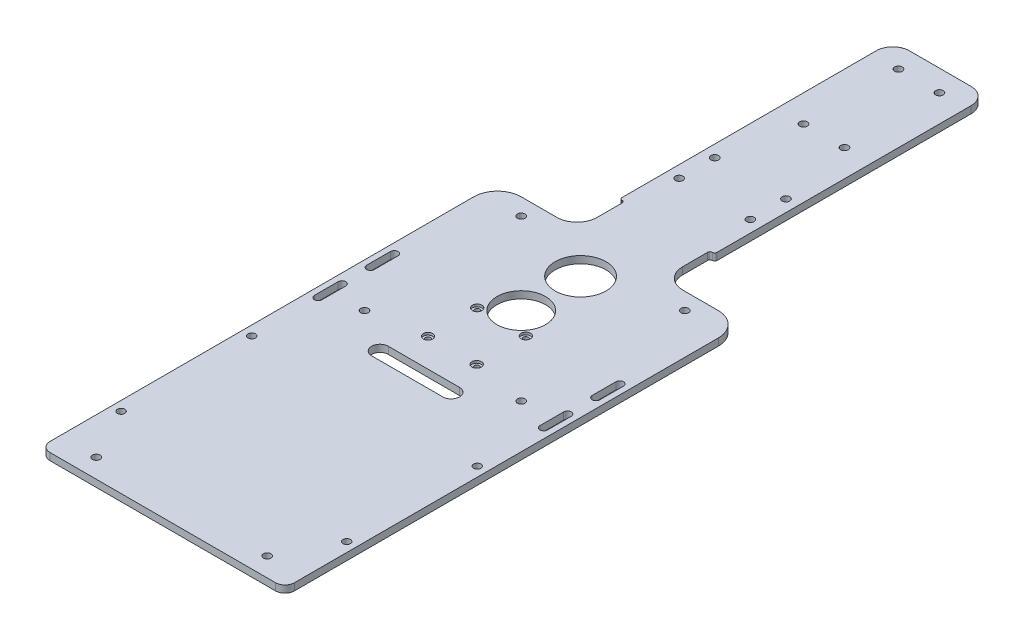
SolidWorks part; units mm, degrees
material "Hexcel AS4C (3000 丝)"
ref_plane "前视基准面" through (0, 0, 0) normal (0, 0, 1) x (1, 0, 0)
ref_plane "上视基准面" through (0, 0, 0) normal (0, 1, 0) x (1, 0, 0)
ref_plane "右视基准面" through (0, 0, 0) normal (1, 0, 0) x (0, 0, -1)
sketch "草图1" plane through (0, 0, 0) normal (0, 1, 0) x (1, 0, 0)
  line L1 (-100, 100) -> (100, 100)
  line L2 (-100, 100) -> (-100, -100)
  line L3 (-100, -100) -> (100, -100)
  line L4 (100, 100) -> (100, -100)
  line L5 (-100, 100) -> (100, -100) construction
  line L6 (-100, -100) -> (100, 100) construction
  point P0 (0, 0)
  dimension "D1" = 200
  dimension "D2" = 200
extrude "凸台-拉伸1" add sketch "草图1" along normal blind 3
sketch "草图2" plane through (0, 3, 0) normal (0, 1, 0) x (1, 0, 0)
  line L0 (0, 0) -> (0, 91) construction
  line L1 (-100, -100) -> (100, -100) construction
  line L2 (100, 100) -> (-100, 100) construction
  line L3 (-100, 0) -> (100, 0) construction
  line L5 (-100, 100) -> (-100, -100) construction
  line L6 (100, -100) -> (100, 100) construction
  line L7 (-29.5, 0) -> (29.5, 0) construction
  line L8 (-10, 100) -> (10, 100) construction
  line L9 (-10, 100) -> (-10, -100) construction
  line L10 (10, 100) -> (10, -100) construction
  line L11 (0, 0) -> (0, -29) construction
  line L13 (0, -29) -> (0, -32) construction
  circle A0 centre (-29.5, 0) radius 22.5 construction
  circle A1 centre (29.5, 0) radius 22.5 construction
  circle A2 centre (0, -29) radius 10.05 construction
  circle A3 centre (29.5, 0) radius 9.5 construction
  circle A4 centre (29.5, 0) radius 8 construction
  circle A5 centre (-29.5, 0) radius 8 construction
  circle A6 centre (-29.5, 0) radius 9.5 construction
  circle A7 centre (29.5, 9.5) radius 1.5
  circle A8 centre (21.5, 0) radius 1.5
  circle A9 centre (29.5, -9.5) radius 1.5
  circle A10 centre (37.5, 0) radius 1.5
  circle A11 centre (-29.5, -9.5) radius 1.5
  circle A12 centre (-37.5, 0) radius 1.5
  circle A13 centre (-21.5, 0) radius 1.5
  circle A14 centre (-29.5, 9.5) radius 1.5
  point P16 (0, 0)
  dimension "D1" = 45
  dimension "D3" = 20.1
  dimension "D4" = 19
  dimension "D5" = 16
  dimension "D6" = 3
  dimension "D7" = 3
  dimension "D2" = 20
  dimension "D9" = 3
  dimension "D10" = 29
extrude "切除-拉伸2" cut sketch "草图2" against normal blind 10
sketch "草图4" plane through (0, 3, 0) normal (0, 1, 0) x (1, 0, 0)
  line L0 (0, 0) -> (0, 91) construction
  line L1 (100, 100) -> (-100, 100) construction
  line L2 (-10, 100) -> (10, 100)
  line L3 (-10, 100) -> (-10, -100) construction
  line L4 (-100, -100) -> (100, -100) construction
  line L5 (10, 100) -> (10, -100) construction
  line L6 (21.5, 0) -> (37.5, 0)
  line L7 (-29.5, 0) -> (0, 0) construction
  line L8 (0, -29) -> (0, 0) construction
  circle A0 centre (0, -29) radius 10.7
  circle A1 centre (29.5, 0) radius 8 construction
  circle A2 centre (29.5, 0) radius 9.5 construction
  circle A3 centre (29.5, 0) radius 22.5 construction
  circle A4 centre (-29.5, 0) radius 9.5 construction
  circle A5 centre (-29.5, 0) radius 8 construction
  circle A6 centre (-29.5, 0) radius 22.5 construction
  dimension "D1" = 21.4
  dimension "D2" = 19
  dimension "D3" = 16
  dimension "D4" = 45
sketch "草图5" plane through (0, 3, 0) normal (0, 1, 0) x (1, 0, 0)
  line L0 (-44.5, -100) -> (-100, -100)
  line L2 (44.5, 0) -> (44.5, -100)
  line L4 (-20, 47.5) -> (-20, 24.995)
  line L6 (-44.5, 0) -> (-44.5, -100)
  line L7 (-100, -100) -> (100, -100) construction
  line L8 (20, 47.5) -> (20, 24.995)
  line L9 (-100, -100) -> (-100, 100)
  line L10 (0, 0) -> (0, 91) construction
  line L11 (0, 47.5) -> (-20, 47.5)
  line L12 (44.5, -100) -> (-44.5, -100)
  line L13 (0, 47.5) -> (20, 47.5)
  line L14 (-100, 100) -> (100, 100)
  line L15 (100, 100) -> (100, -100)
  line L16 (100, -100) -> (44.5, -100)
  arc A0 (29.8, 14.997) -> (44.5, 0) centre (29.5, 0) cw
  arc A1 (20, 24.995) -> (29.8, 14.997) centre (30, 24.995) ccw
  arc A2 (-29.8, 14.997) -> (-44.5, 0) centre (-29.5, 0) ccw
  arc A3 (-20, 24.995) -> (-29.8, 14.997) centre (-30, 24.995) cw
  line M11 (100, -100) -> (100, 100)
  line M12 (100, 100) -> (-100, 100)
  line M13 (-100, 100) -> (-100, -100)
  line M14 (-100, -100) -> (100, -100)
  dimension "D1" = 10
  dimension "D2" = 15
extrude "切除-拉伸3" cut sketch "草图5" against normal blind 10 contours A3 L4 L11 L13 L8 A1 A0 L2 L6 A2 M14 M11 M12 M13 region at (-72.25, 3, 97.1716)
sketch "草图6" plane through (0, 0, 0) normal (0, -1, 0) x (1, 0, 0)
  line L0 (20, -47.5) -> (-20, -47.5) construction
  line L7 (-20, -47.5) -> (-20, -24.995) construction
  circle A1 centre (-15, -42.5) radius 1.6
  circle A2 centre (-15, -27.5) radius 1.6
  circle A3 centre (15, -27.5) radius 1.6
  circle A4 centre (15, -42.5) radius 1.6
  dimension "D1" = 3.2
  dimension "D5" = 3.2
  dimension "D6" = 3.2
  dimension "D7" = 3.2
  dimension "D2" = 5
  dimension "D3" = 5
  dimension "D4" = 30
extrude "φ3.1通孔1" cut sketch "草图6" against normal blind 10
sketch "草图9" plane through (0, 3, 0) normal (0, 1, 0) x (1, 0, 0)
  line L0 (-20, 47.5) -> (-20, 26.3383)
  line L4 (-20, 47.5) -> (20, 47.5)
  line L5 (20, 47.5) -> (20, 26.3383)
  line L8 (12.2609, 20.995) -> (-12.2609, 20.995)
  arc A0 (-18.8003, 24.5054) -> (-13.4605, 21.3948) centre (-29.5, 0) cw
  arc A1 (18.8003, 24.5054) -> (13.4605, 21.3948) centre (29.5, 0) ccw
  arc A2 (18.8003, 24.5054) -> (20, 26.3383) centre (18, 26.3383) ccw
  arc A3 (13.4605, 21.3948) -> (12.2609, 20.995) centre (12.2609, 22.995) cw
  arc A4 (-12.2609, 20.995) -> (-13.4605, 21.3948) centre (-12.2609, 22.995) cw
  arc A5 (-18.8003, 24.5054) -> (-20, 26.3383) centre (-18, 26.3383) cw
  point P20 (-20, 24.995)
  dimension "D1" = 2
sketch "草图11" plane through (0, 3, 0) normal (0, 1, 0) x (1, 0, 0)
  line L0 (44.5, -17.5) -> (44.5, -100)
  line L1 (20, 47.5) -> (20, 7.5)
  line L2 (-44.5, 0) -> (-44.5, -100) construction
  line L3 (-44.5, -17.5) -> (-44.5, -100)
  line L4 (0, 47.5) -> (0, -100) construction
  line L5 (20, 47.5) -> (-20, 47.5) construction
  line L6 (-44.5, -100) -> (44.5, -100) construction
  line L7 (18, -4) -> (18, 6.5)
  line L8 (20, 7.5) -> (19, 7.5)
  line L9 (-39.5, -12.5) -> (-44.5, -12.5)
  line L10 (26.5, -12.5) -> (39.5, -12.5)
  line L11 (20, 47.5) -> (101.1331, 47.5)
  line L12 (101.1331, 47.5) -> (101.1331, -100)
  line L13 (101.1331, -100) -> (44.5, -100)
  line L14 (-20, 47.5) -> (-20, 7.5)
  line L15 (-20, 7.5) -> (-19, 7.5)
  line L16 (-18, -4) -> (-18, 6.5)
  line L17 (-26.5, -12.5) -> (-39.5, -12.5)
  line L18 (-44.5, -12.5) -> (-44.5, -17.5)
  line L19 (-101.1331, -100) -> (-44.5, -100)
  line L20 (-101.1331, 47.5) -> (-101.1331, -100)
  line L21 (-20, 47.5) -> (-101.1331, 47.5)
  line L22 (39.5, -12.5) -> (44.5, -12.5)
  line L23 (44.5, 0) -> (44.5, -100) construction
  line L24 (44.5, -12.5) -> (44.5, -17.5)
  arc A0 (26.5, -12.5) -> (18, -4) centre (26.5, -4) cw
  circle A2 centre (29.5, -9.5) radius 1.5
  circle A4 centre (21.5, 0) radius 1.5
  arc A5 (18, 6.5) -> (19, 7.5) centre (19, 6.5) cw
  arc A6 (-18, 6.5) -> (-19, 7.5) centre (-19, 6.5) ccw
  arc A7 (-26.5, -12.5) -> (-18, -4) centre (-26.5, -4) ccw
  point P21 (-44.5, -12.5)
  dimension "D1" = 8.5
  dimension "D2" = 1
extrude "切除-拉伸6" cut sketch "草图11" against normal up to next
extrude "φ21.4落弹孔" cut sketch "草图4" against normal up to next contours A0 region at (0, 3, 29)
fillet "圆角1" radius 1 2 edges at (-20, 1.5, -7.5) (20, 1.5, -7.5)
sketch "草图12" plane through (0, 0, -47.5) normal (0, 0, -1) x (-1, 0, 0)
  line L0 (-20, 3) -> (-20, 0)
  line L1 (-20, 0) -> (20, 0)
  line L2 (20, 0) -> (20, 3)
  line L3 (20, 3) -> (-20, 3)
extrude "凸台-拉伸2" add sketch "草图12" along normal blind 75
fillet "圆角2" radius 7 2 edges at (-20, 1.5, -122.5) (20, 1.5, -122.5)
sketch "草图13" plane through (0, 3, 0) normal (0, 1, 0) x (1, 0, 0)
  line L0 (-20, 115.5) -> (-20, 8.5) construction
  line L1 (0, 122.5) -> (0, 107.278)
  line L2 (-13, 122.5) -> (13, 122.5) construction
  circle A0 centre (-8.625, 73.5) radius 1.6
  circle A1 centre (-15, 42.5) radius 1.55
  circle A2 centre (-8.625, 113.5) radius 1.6
  circle A3 centre (8.625, 73.5) radius 1.6
  circle A4 centre (8.625, 113.5) radius 1.6
  dimension "D3" = 3.2
  dimension "D5" = 3.2
  dimension "D1" = 31
  dimension "D2" = 11.375
  dimension "D4" = 40
extrude "φ3.2通孔3" cut sketch "草图13" against normal blind 10 contours A2 | A4 | A3 | A0 region at (-8.625, 3, -73.5) region at (-8.625, 3, -113.5) region at (8.625, 3, -73.5) region at (8.625, 3, -113.5)
sketch "草图19" plane through (0, 0, 100) normal (0, 0, 1) x (1, 0, 0)
  line L0 (-44.5, 3) -> (-44.5, 0)
  line L1 (-44.5, 0) -> (44.5, 0)
  line L2 (44.5, 0) -> (44.5, 3)
  line L3 (44.5, 3) -> (-44.5, 3)
extrude "凸台-拉伸3" add sketch "草图19" along normal blind 105
sketch "草图14" plane through (0, 3, 0) normal (0, 1, 0) x (1, 0, 0)
  line L0 (0, -54) -> (0, -49.4646) construction
  line L1 (0, -43) -> (32.1524, -43) construction
  circle A0 centre (0, -29) radius 11 construction
  circle A1 centre (0, -54) radius 10.25
  point P19 (0, -54)
  dimension "D1" = 22
  dimension "D2" = 20.5
extrude "舵机轴孔" cut sketch "草图14" against normal up to next
sketch "草图20" plane through (0, 3, 0) normal (0, 1, 0) x (1, 0, 0)
  line L0 (0, -54) -> (0, -59.9889) construction
  circle A0 centre (0, -54) radius 10.5
  circle A1 centre (10.25, -62.3) radius 1.05
  circle A2 centre (10.25, -83) radius 1.05
  circle A3 centre (-10.25, -83) radius 1.05
  circle A4 centre (-10.25, -62.3) radius 1.05
  dimension "D3" = 2.1
  dimension "D5" = 2.1
  dimension "D1" = 10.25
  dimension "D2" = 8.3
  dimension "D4" = 20.7
hole_wizard "孔1" positions "3D草图1" profile "草图21" legacy end condition through all
sketch3d "3D草图1"
  point P0 (-10.25, 3, 62.3)
  point P3 (10.25, 3, 62.3)
  point P6 (-10.25, 3, 83)
  point P9 (10.25, 3, 83)
sketch "草图21" plane through (-10.25, 3, 62.3) normal (1, 0, 0) x (0, 0, 1)
  line L0 (0, 0) -> (0, 3)
  line L1 (0, 3) -> (1.1, 3)
  line L2 (1.1, 3) -> (1.1, 1)
  line L3 (1.1, 1) -> (2, 1)
  line L4 (2, 0) -> (0, 0)
  line L5 (0, -11.3109) -> (0, 121.1557) construction
  line L6 (0, 3) -> (-1.1, 3) construction
  line L7 (2, 1) -> (2, 0)
  dimension "直径" = 2.2
  dimension "深度" = 3
  dimension "柱坑直径" = 4
  dimension "柱坑深度" = 1
  dimension "导头角度" = 180
sketch "草图23" plane through (0, 3, 0) normal (0, 1, 0) x (1, 0, 0)
  line L0 (0, -54) -> (0, -87) construction
  circle A0 centre (33, -87) radius 1.6
  circle A1 centre (-33, -87) radius 1.6
  dimension "D3" = 3.2
  dimension "D1" = 33
  dimension "D2" = 33
extrude "切除-拉伸8" cut sketch "草图23" against normal up to next
sketch "草图24" plane through (-44.5, 0, 0) normal (-1, 0, 0) x (0, 0, 1)
  line L0 (12.5, 3) -> (12.5, 0)
  line L1 (12.5, 0) -> (205, 0)
  line L2 (205, 0) -> (205, 3)
  line L3 (205, 3) -> (12.5, 3)
extrude "凸台-拉伸4" add sketch "草图24" along normal blind 7
mirror "镜向2" about plane through (0, 0, 0) normal (1, 0, 0) of "凸台-拉伸4"
fillet "圆角3" radius 10 2 edges at (51.5, 1.5, 12.5) (-51.5, 1.5, 12.5)
sketch "草图17" plane through (0, 3, 0) normal (0, 1, 0) x (1, 0, 0)
  line L0 (-49.1, -70) -> (-49.1, -60)
  line L2 (49.1, -87) -> (45.9, -87) construction
  line L3 (-45.9, -70) -> (-45.9, -60)
  line L4 (-49.1, -92) -> (-49.1, -82)
  line L5 (-45.9, -65) -> (-49.1, -65) construction
  line L6 (-45.9, -92) -> (-45.9, -82)
  line L7 (0, -54) -> (0, -74.1004) construction
  line L8 (-49.1, -87) -> (-45.9, -87) construction
  line L9 (45.9, -65) -> (49.1, -65) construction
  line L10 (45.9, -92) -> (45.9, -82)
  line L11 (49.1, -92) -> (49.1, -82)
  line L12 (45.9, -70) -> (45.9, -60)
  line L13 (49.1, -70) -> (49.1, -60)
  arc A0 (-45.9, -70) -> (-49.1, -70) centre (-47.5, -70) cw
  arc A1 (-45.9, -92) -> (-49.1, -92) centre (-47.5, -92) cw
  arc A2 (45.9, -82) -> (49.1, -82) centre (47.5, -82) cw
  arc A3 (45.9, -60) -> (49.1, -60) centre (47.5, -60) cw
  arc A4 (-45.9, -60) -> (-49.1, -60) centre (-47.5, -60) ccw
  arc A5 (-45.9, -82) -> (-49.1, -82) centre (-47.5, -82) ccw
  arc A6 (45.9, -92) -> (49.1, -92) centre (47.5, -92) ccw
  arc A7 (45.9, -70) -> (49.1, -70) centre (47.5, -70) ccw
  dimension "D1" = 65
extrude "上下板后固定孔" cut sketch "草图17" against normal blind 7
sketch "草图22" plane through (0, 3, 0) normal (0, 1, 0) x (1, 0, 0)
  line L0 (0, -54) -> (0, -48.7978) construction
  circle A0 centre (-36, -197) radius 1.6
  circle A1 centre (36, -197) radius 1.6
  point P2 (0, -54)
  dimension "D3" = 3.2
  dimension "D1" = 143
  dimension "D2" = 36
extrude "切除-拉伸7" cut sketch "草图22" against normal up to next
sketch "草图16" plane through (0, 3, 0) normal (0, 1, 0) x (1, 0, 0)
  line L0 (0, -54) -> (-34.4467, -19.5533) construction
  line L1 (0, -54) -> (0, -33.1135) construction
  circle A0 centre (-34.4467, -19.5533) radius 1.6
  circle A1 centre (0, -54) radius 44 construction
  circle A3 centre (34.4467, -19.5533) radius 1.6
  dimension "D1" = 88
  dimension "D3" = 3.2
extrude "切除-拉伸9" cut sketch "草图16" against normal blind 10
sketch "草图25" plane through (0, 3, 0) normal (0, 1, 0) x (1, 0, 0)
  line L0 (0, -54) -> (0, -95) construction
  line L1 (41, -95) -> (-41, -95) construction
  line L2 (-41, -95) -> (-41, -202) construction
  line L3 (41, -95) -> (41, -202) construction
  line L4 (-27.5, -187) -> (27.5, -187) construction
  line L5 (-27.5, -102) -> (27.5, -102) construction
  line L6 (-27.5, -102) -> (-27.5, -187) construction
  line L7 (27.5, -102) -> (27.5, -187) construction
  line L8 (-41, -202) -> (41, -202) construction
  line L9 (-15, -95) -> (15, -95)
  line L10 (-15, -102) -> (15, -102)
  line L12 (-27.5, -102) -> (27.5, -102) construction
  circle A0 centre (0, -54) radius 35 construction
  arc A1 (-15, -95) -> (-15, -102) centre (-15, -98.5) ccw
  arc A2 (15, -95) -> (15, -102) centre (15, -98.5) cw
  dimension "D1" = 70
  dimension "D2" = 107
  dimension "D3" = 15
  dimension "D4" = 7
  dimension "D5" = 55
  dimension "D6" = 85
  dimension "D7" = 30
extrude "穿线孔" cut sketch "草图25" against normal blind 10
sketch "草图26" plane through (0, 3, 0) normal (0, 1, 0) x (1, 0, 0)
  line L0 (0, -54) -> (0, -95) construction
  line L1 (41, -95) -> (-41, -95) construction
  line L2 (-41, -95) -> (-41, -202) construction
  line L3 (41, -95) -> (41, -202) construction
  line L4 (-27.5, -187) -> (27.5, -187) construction
  line L5 (-27.5, -102) -> (27.5, -102) construction
  line L6 (-27.5, -102) -> (-27.5, -187) construction
  line L7 (27.5, -102) -> (27.5, -187) construction
  line L8 (-41, -202) -> (41, -202) construction
  line L9 (-20, -95) -> (20, -95) construction
  line L10 (-20, -102) -> (20, -102) construction
  line L11 (-27.5, -102) -> (27.5, -102) construction
  circle A0 centre (0, -54) radius 35 construction
  arc A1 (-20, -95) -> (-20, -102) centre (-20, -98.5) ccw construction
  arc A2 (20, -95) -> (20, -102) centre (20, -98.5) cw construction
  circle A3 centre (12.5, -106) radius 1.6
  circle A4 centre (-12.5, -106) radius 1.6
  circle A5 centre (-14.1, -177) radius 1.6
  point P17 (0, -54)
  dimension "D2" = 3.2
  dimension "D4" = 3.2
  dimension "D1" = 4
  dimension "D3" = 12.5
  dimension "D5" = 10
  dimension "D6" = 13.4
sketch "草图27" plane through (0, 3, 0) normal (0, 1, 0) x (1, 0, 0)
  line L0 (51.5, -205) -> (-51.5, -205) construction
  line L1 (-51.5, -205) -> (-51.5, -22.5) construction
  line L2 (0, -130.3131) -> (0, -154.6099) construction
  circle A0 centre (-47.5, -175) radius 1.55
  circle A1 centre (-47.5, -120) radius 1.55
  circle A2 centre (47.5, -120) radius 1.55
  circle A3 centre (47.5, -175) radius 1.55
  dimension "D1" = 3.1
  dimension "D4" = 3.1
  dimension "D6" = 4
  dimension "D2" = 30
  dimension "D3" = 4
  dimension "D5" = 55
hole_wizard "Ø3.1 (3.1) 直径孔1" positions "3D草图2" profile "草图28" hole size "Ø3.1" standard "GB" end condition through all
sketch3d "3D草图2"
  point P0 (-47.5, 3, 120)
  point P3 (47.5, 3, 120)
  point P6 (47.5, 3, 175)
  point P9 (-47.5, 3, 175)
sketch "草图28" plane through (-47.5, 3, 120) normal (1, 0, 0) x (0, 0, 1)
  line L0 (0, 0) -> (0, 3)
  line L1 (0, 3) -> (1.55, 3)
  line L2 (1.55, 3) -> (1.55, 0)
  line L5 (1.55, 0) -> (0, 0)
  line L11 (0, -6.35) -> (0, 107.95) construction
  dimension "通孔孔直径" = 3.1
  dimension "通孔孔深度" = 3
fillet "圆角4" radius 4 2 edges at (51.5, 1.5, 205) (-51.5, 1.5, 205)
